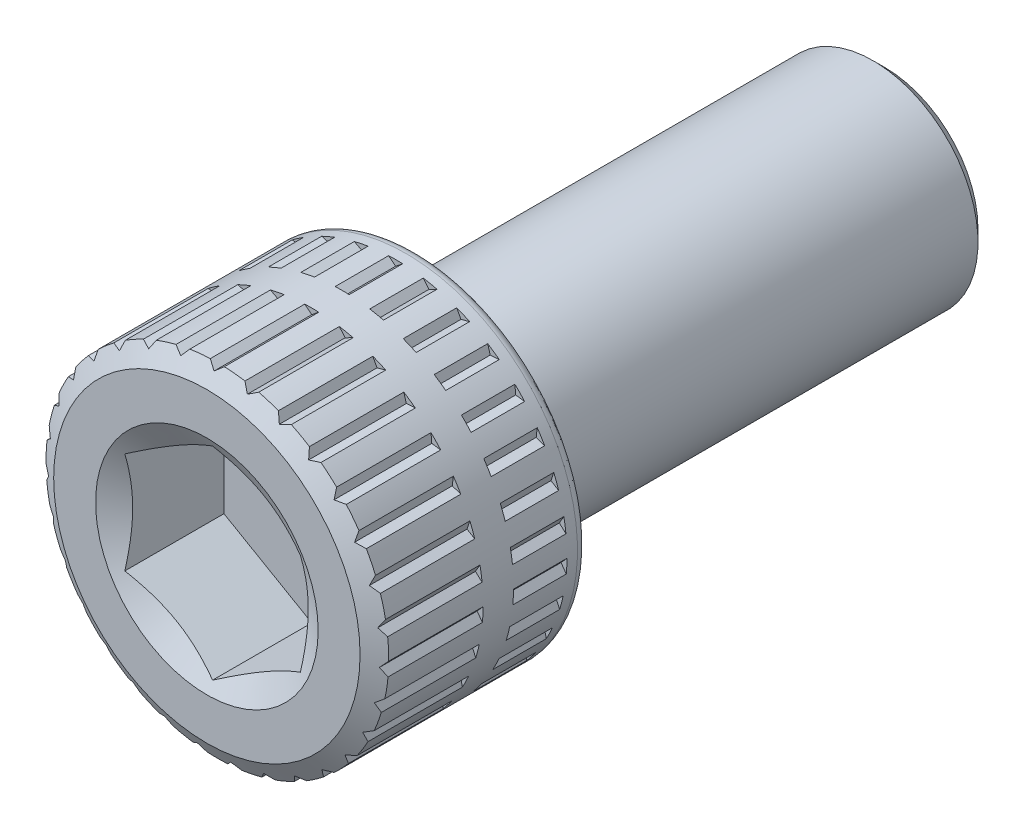
SolidWorks part; units mm, degrees
material "6061-T6 (SS)"
ref_plane "Front Plane" through (0, 0, 0) normal (0, 0, 1) x (1, 0, 0)
ref_plane "Top Plane" through (0, 0, 0) normal (0, 1, 0) x (1, 0, 0)
ref_plane "Right Plane" through (0, 0, 0) normal (1, 0, 0) x (0, 0, -1)
sketch "Sketch1" plane through (0, 0, 0) normal (1, 0, 0) x (0, 0, -1)
  line L0 (4.5974, 0) -> (-4.5974, 0) construction
  line L1 (-1.7526, 2.3241) -> (-1.7526, -2.3241) construction
  line L2 (4.5974, 1.4224) -> (4.5974, -1.4224) construction
  line L3 (4.5577, 1.4911) -> (4.8752, 0.9412) construction
  line L4 (4.8355, 1.01) -> (4.9149, 1.01) construction
  line L5 (4.8752, 0.9412) -> (5.1927, 1.4911) construction
  line L6 (5.1927, 1.4911) -> (4.5577, 1.4911) construction
  line L7 (4.8752, 1.01) -> (4.8752, 0.9412) construction
  line L8 (4.8752, 1.4911) -> (4.8752, 1.4224) construction
  line L9 (5.153, 1.4224) -> (4.5974, 1.4224) construction
  point P4 (-1.7526, 0)
  point P6 (-1.7526, 1.1906)
  point P7 (2.3749, -1.4224)
  point P20 (4.8752, 1.4568)
sketch "Sketch2" plane through (0, 0, 0) normal (1, 0, 0) x (0, 0, -1)
  line L0 (4.5974, 0) -> (4.5974, 1.2637)
  line L1 (4.5974, 1.4224) -> (4.5974, -1.4224) construction
  line L2 (4.5974, 1.2637) -> (4.4387, 1.4224)
  line L3 (4.4387, 1.4224) -> (-1.7526, 1.4224)
  line L4 (-1.7526, 1.4224) -> (-1.7526, 2.1819)
  line L5 (-1.8948, 2.3241) -> (-4.4552, 2.3241)
  line L6 (-4.5974, 2.1819) -> (-4.5974, 0)
  line L7 (4.5974, 0) -> (-4.5974, 0) construction
  line L8 (-4.5974, 0) -> (4.5974, 0)
  arc A0 (-1.7526, 2.1819) -> (-1.8948, 2.3241) centre (-1.8948, 2.1819) ccw
  arc A1 (-4.4552, 2.3241) -> (-4.5974, 2.1819) centre (-4.4552, 2.1819) ccw
  point P19 (-1.7526, 2.3241)
  dimension "D1" = 0.1588
  dimension "D2" = 45
revolve "Revolve1" add sketch "Sketch2" angle 360 about L0
sketch "Sketch3" plane through (0, 0, 0) normal (0, 0, 1) x (1, 0, 0)
  line L1 (-1.1906, 0.6874) -> (-1.1906, -0.6874)
  line L2 (-1.1906, -0.6874) -> (0, -1.3748)
  line L3 (0, -1.3748) -> (1.1906, -0.6874)
  line L4 (1.1906, -0.6874) -> (1.1906, 0.6874)
  line L5 (1.1906, 0.6874) -> (0, 1.3748)
  line L6 (0, 1.3748) -> (-1.1906, 0.6874)
  circle A0 centre (0, 0) radius 1.1906 construction
  circle A1 centre (0, 0) radius 2.3241 construction
extrude "Cut-Extrude1" cut sketch "Sketch3" against normal blind 1.4224 from vertex starting at point (0, 0, 4.5974)
sketch "Sketch4" plane through (0, 0, 4.5974) normal (0, 0, 1) x (1, 0, 0)
  line L0 (0, 1.3748) -> (0, 1.6438) construction
  line L1 (0, 1.6438) -> (0, 1.9128) construction
  line L2 (0, 1.9128) -> (0, 2.1819) construction
  circle A0 centre (0, 0) radius 1.5093
  point P12 (0, 1.5093)
extrude "Cut-Extrude2" cut sketch "Sketch4" against normal through all draft 60
split "Split1" [suppressed] bodies to split 106 112
sketch "Sketch5" [suppressed] plane through (0, 0, 0) normal (1, 0, 0) x (0, 0, -1)
  line L0 (4.8355, 1.01) -> (4.9149, 1.01)
  line L1 (4.9149, 1.01) -> (5.1729, 1.4568)
  line L2 (5.1729, 1.4568) -> (4.5776, 1.4568)
  line L3 (4.5776, 1.4568) -> (4.8355, 1.01)
  line L4 (4.5577, 1.4911) -> (4.8752, 0.9412) construction
sketch "Sketch6" [suppressed] plane through (0, 0, -4.5974) normal (0, 0, -1) x (-1, 0, 0)
  circle A0 centre (0, 0) radius 1.4224
curve "Helix/Spiral1" [suppressed] pitch 0.635 height 6.985 turns 11
sweep "Cut-Sweep1" [suppressed] cut profiles "Sketch5" path "Helix/Spiral1"
sketch "Sketch7" [suppressed] plane through (0, 0, 1.7526) normal (0, 0, -1) x (-1, 0, 0)
  circle A0 centre (0, 0) radius 1.4732
  circle A1 centre (0, 0) radius 1.4224 construction
  dimension "D1" = 0.0508
extrude "Boss-Extrude1" [suppressed] add sketch "Sketch7" along normal through all draft 20 and the other way blind 0.2845
ref_plane "Plane1" through (0, 0, 2.0371) normal (0, 0, -1) x (-1, 0, 0)
other "DeleteFace1" face at (-2.1819, 0, 4.5974) and patch yes
chamfer "Chamfer1" distance 0.1422 angle 60 1 edges at (2.3241, 0, 4.5974) first distance on face at (2.3241, 0, 4.5974)
sketch "Sketch8" plane through (0, 0, 2.0371) normal (0, 0, -1) x (-1, 0, 0)
  line L0 (0.0953, 2.3221) -> (0, 0) construction
  line L1 (0, 0) -> (-0.0952, 2.3221) construction
  line L7 (-0.0952, 2.3221) -> (0, 2.2459)
  line L8 (0, 2.2459) -> (0.0953, 2.3221)
  arc A1 (0.0953, 2.3221) -> (-0.0952, 2.3221) centre (0, 0) ccw
  circle A2 centre (0, 0) radius 2.3241 construction
  point P2 (0, 2.3241)
  dimension "D3" = 0.0762
  dimension "D1" = 0.1905
extrude "Cut-Extrude3" cut sketch "Sketch8" against normal blind 0.7254
extrude "Cut-Extrude4" cut sketch "Sketch8<4>" against normal through all from offset 1.1379 offset against normal yes
sketch "Sketch8<4>" plane through (0, 0, 2.0371) normal (0, 0, -1) x (-1, 0, 0) same geometry as "Sketch8"
pattern_circular "CirPattern1" count 31 over 360 about axis through (0, 0, -4.5974) along (0, 0, 1) of "Cut-Extrude3", "Cut-Extrude4" reverse direction yes
equation "\"Pitch/8@Sketch1\" = \"Pitch@Sketch1\" / 8"
equation "\"Thread Note@Sketch1\" = \"Pitch@Sketch1\" * 3.5"
equation "\"D1@Sketch2\"=\"Pitch@Sketch1\"*.25"
equation "\"D3@Sketch2\"=\"Head Height@Sketch1\"*.05"
equation "\"D1@Cut-Extrude1\" = \"Head Height@Sketch1\" * .5"
equation "\"D3@Helix/Spiral1\" = \"Length@Sketch1\" + \"Pitch@Sketch1\""
equation "\"D4@Helix/Spiral1\" = \"Pitch@Sketch1\""
equation "\"D2@Boss-Extrude1\" = \"Head Height@Sketch1\" * .1"
equation "\"D1\"= \"Screw Size Decimal Equivalent@Sketch1\" * .4"
equation "\"D1@Plane1\" = \"D3@Sketch2\" * 2"
equation "\"D1@Cut-Extrude3\"=( \"Head Height@Sketch1\" - \"D1@Plane1\" - \"D3@Sketch2\" )  * .3"
equation "\"D1@CirPattern1\" =  ( \"Head Diameter@Sketch1\" * pi )  /  ( 2.5 * \"D1@Sketch8\" ) "
equation "\"D1@Chamfer1\" = \"D3@Sketch2\""
equation "\"D19@Cut-Extrude4\" =  ( \"Head Height@Sketch1\" * .5 )  - \"D1@Plane1\""
